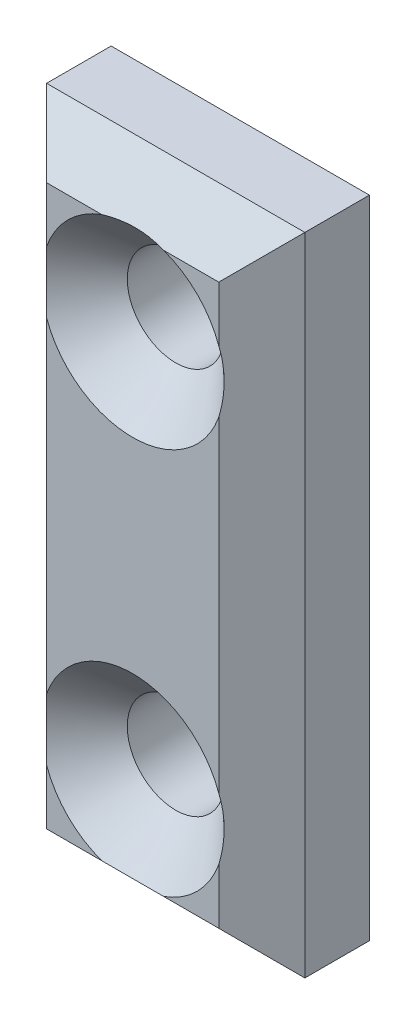
SolidWorks part; units mm, degrees
ref_plane "Front Plane" through (0, 0, 0) normal (0, 0, 1) x (1, 0, 0)
ref_plane "Top Plane" through (0, 0, 0) normal (0, 1, 0) x (1, 0, 0)
ref_plane "Right Plane" through (0, 0, 0) normal (1, 0, 0) x (0, 0, -1)
sketch "Sketch1" plane through (0, 0, 0) normal (0, 0, 1) x (1, 0, 0)
  line L1 (133.5617, 73.8) -> (121.5617, 73.8)
  line L2 (133.5617, 73.8) -> (133.5617, 43.8)
  line L9 (133.5617, 43.8) -> (121.5617, 43.8)
  line L10 (121.5617, 73.8) -> (121.5617, 43.8)
  line L11 (133.5617, 73.8) -> (121.5617, 43.8) construction
  line L12 (133.5617, 43.8) -> (121.5617, 73.8) construction
  point P4 (127.5617, 58.8)
  dimension "D2" = 30
  dimension "D3" = 12
extrude "Boss-Extrude1" add sketch "Sketch1" along normal blind 5
sketch "Sketch2" plane through (0, 0, 5) normal (0, 0, 1) x (1, 0, 0)
  circle A0 centre (127.5617, 67.8) radius 2.25
  circle A1 centre (127.5617, 49.8) radius 2.25
extrude "Cut-Extrude1" cut sketch "Sketch2" against normal through all
chamfer "Chamfer1" distance 2 angle 45 6 edges at (127.5617, 73.8, 5) (133.5617, 58.8, 5) (127.5617, 43.8, 5) (121.5617, 58.8, 5) (129.8117, 49.8, 5) (129.8117, 67.8, 5)
